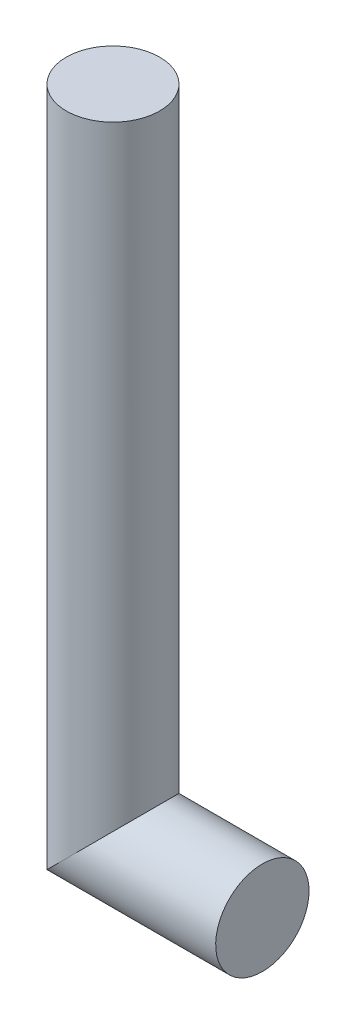
SolidWorks part; units mm, degrees
ref_plane "Front Plane" through (0, 0, 0) normal (0, 0, 1) x (1, 0, 0)
ref_plane "Top Plane" through (0, 0, 0) normal (0, 1, 0) x (1, 0, 0)
ref_plane "Right Plane" through (0, 0, 0) normal (1, 0, 0) x (0, 0, -1)
sketch "Sketch1" plane through (0, 0, 0) normal (0, 0, 1) x (1, 0, 0)
  line L0 (120, 0) -> (0, 0)
  line L1 (0, 0) -> (0, 300)
sweep "Sweep2" add path "Sketch1" circular profile diameter 75 parameters "D3"=75
ref_axis "Axis1" through (120, 0, 0) along (-1, 0, 0)
ref_axis "Axis2" through (0, -37.5, 0) along (0, 1, 0)
ref_point "Point1"
ref_axis "Axis3" through (0, 0, 0) along (0, 0, 1)
ref_point "Point2"
sketch "Sketch40" plane through (0, 0, 0) normal (0, 0, 1) x (1, 0, 0)
  line L0 (123.6742, 0) -> (0, 0) construction
ref_point "Point3"
ref_axis "Axis4" through (74.2045, 0, 0) along (0, 0, 1)
other "Move Face1" face at (0, 300, -37.5) offset 100 parameters "D1"=100
other "Move Face2" face at (0, 400, -37.5) offset 120 parameters "D1"=120
